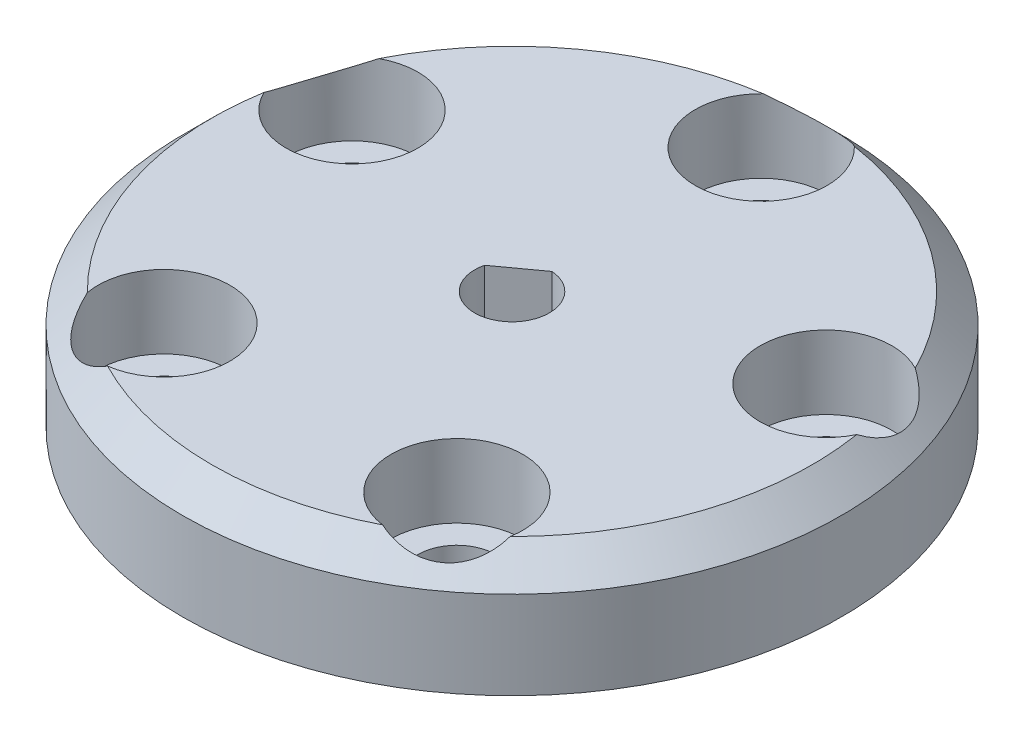
SolidWorks part; units mm, degrees
ref_plane "Front Plane" through (0, 0, 0) normal (0, 0, 1) x (1, 0, 0)
ref_plane "Top Plane" through (0, 0, 0) normal (0, 1, 0) x (1, 0, 0)
ref_plane "Right Plane" through (0, 0, 0) normal (1, 0, 0) x (0, 0, -1)
sketch "Sketch1" plane through (0, 0, 0) normal (0, 1, 0) x (1, 0, 0)
  line L1 (10, -13.7638) -> (16.1803, 5.2573) construction
  line L2 (16.1803, 5.2573) -> (0, 17.013) construction
  line L3 (0, 17.013) -> (-16.1803, 5.2573) construction
  line L4 (-16.1803, 5.2573) -> (-10, -13.7638) construction
  line L5 (-10, -13.7638) -> (10, -13.7638) construction
  circle A0 centre (0, 0) radius 13.7638 construction
  circle A15 centre (0, 0) radius 25.013 construction
  circle A16 centre (0, 17.013) radius 8 construction
  circle A17 centre (16.1803, 5.2573) radius 8 construction
  circle A18 centre (10, -13.7638) radius 8 construction
  circle A19 centre (-10, -13.7638) radius 8 construction
  circle A22 centre (-16.1803, 5.2573) radius 8 construction
  circle A23 centre (0, 0) radius 22.5
  circle A24 centre (0, 17.013) radius 2.65
  circle A25 centre (-16.1803, 5.2573) radius 2.65
  circle A26 centre (-10, -13.7638) radius 2.65
  circle A27 centre (10, -13.7638) radius 2.65
  circle A28 centre (16.1803, 5.2573) radius 2.65
  dimension "D1" = 16
  dimension "D2" = 20
  dimension "D3" = 45
  dimension "D4" = 5.3
extrude "Boss-Extrude1" add sketch "Sketch1" along normal blind 8
sketch "Sketch2" plane through (0, 8, 0) normal (0, 1, 0) x (1, 0, 0)
  circle A0 centre (-16.1803, 5.2573) radius 4.5
  circle A1 centre (0, 17.013) radius 4.5
  circle A2 centre (16.1803, 5.2573) radius 4.5
  circle A3 centre (10, -13.7638) radius 4.5
  circle A4 centre (-10, -13.7638) radius 4.5
  dimension "D1" = 9
extrude "Cut-Extrude1" cut sketch "Sketch2" against normal blind 5
chamfer "Chamfer1" distance 2 angle 45 1 edges at (0, 8, 22.5)
sketch "Sketch3" plane through (0, 0, 0) normal (0, -1, 0) x (1, 0, 0)
  line L0 (0.1832, -2.5434) -> (-2.4755, -0.6118)
  line L1 (0.1832, -2.5434) -> (-2.4755, -0.6118) construction
  arc A0 (0.1832, -2.5434) -> (-2.4755, -0.6118) centre (0, 0) ccw
  point P1 (1.4989, 2.063)
  point P5 (0.62, 2.4735)
  point P6 (0, 0)
  dimension "D2" = 4.5
extrude "Cut-Extrude3" cut sketch "Sketch3" against normal through all contours A0 L0
